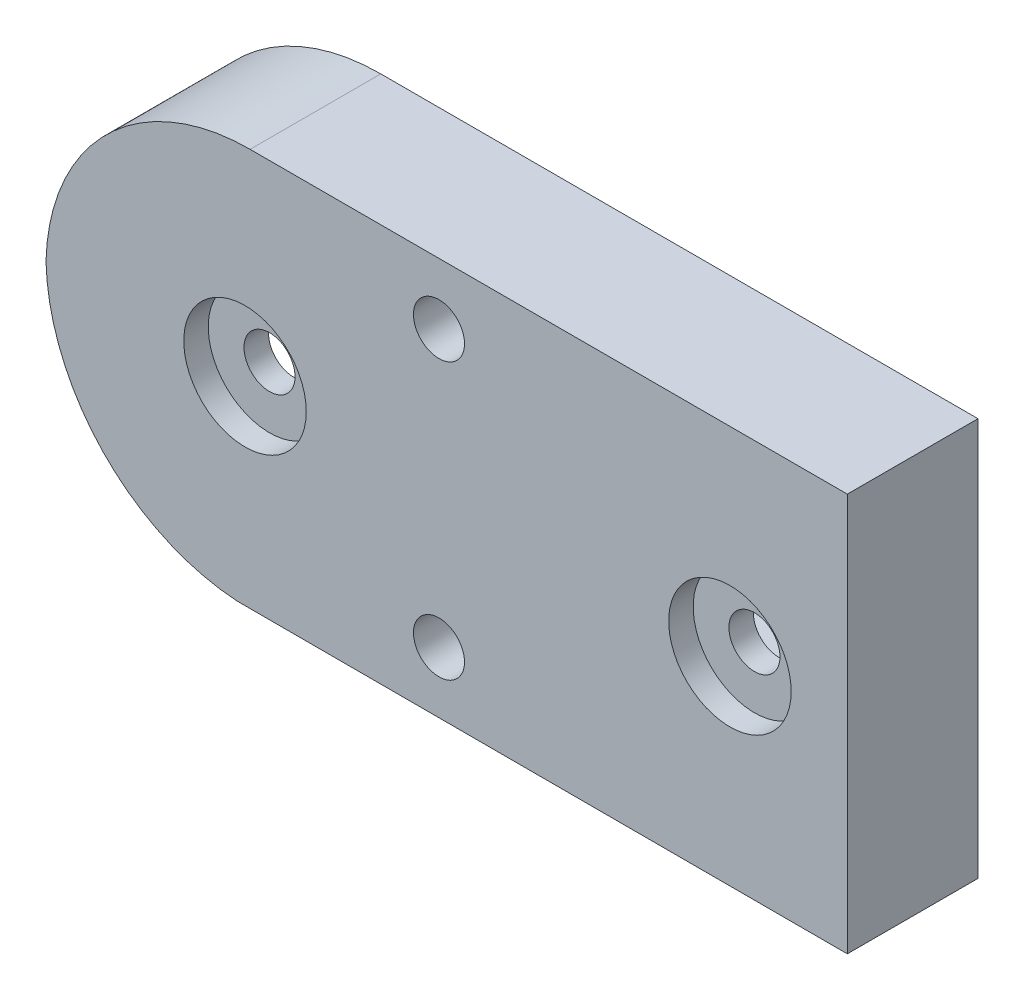
SolidWorks part; units mm, degrees
ref_plane "Front Plane" through (0, 0, 0) normal (0, 0, 1) x (1, 0, 0)
ref_plane "Top Plane" through (0, 0, 0) normal (0, 1, 0) x (1, 0, 0)
ref_plane "Right Plane" through (0, 0, 0) normal (1, 0, 0) x (0, 0, -1)
sketch "Sketch1" plane through (0, 0, 0) normal (0, 0, 1) x (1, 0, 0)
  line L0 (0, 0) -> (23.75, 0)
  line L1 (23.75, 3.75) -> (6.7823, 3.75)
  line L2 (23.75, -3.75) -> (6.7823, -3.75)
  line L3 (0, 0) -> (-9.75, 0)
  line L4 (-9.75, -9.75) -> (-9.75, 9.75)
  line L5 (-9.75, 9.75) -> (29.5, 9.75)
  line L6 (29.5, 9.75) -> (29.5, -9.75)
  line L7 (-9.75, -9.75) -> (29.5, -9.75)
  line L8 (29.5, 9.75) -> (29.5, 6.75)
  line L9 (29.5, 6.75) -> (9.5, 6.75)
  line L10 (29.5, -9.75) -> (29.5, -6.75)
  line L11 (29.5, -6.75) -> (9.5, -6.75)
  circle A0 centre (0, 0) radius 7.75
  circle A1 centre (23.75, 0) radius 3.75
  arc A2 (4.901, 6.0035) -> (11.225, 3.75) centre (11.225, 13.75) ccw
  arc A3 (11.225, -3.75) -> (4.901, -6.0035) centre (11.225, -13.75) ccw
  circle A4 centre (9.5, 6.75) radius 1.25
  circle A6 centre (9.5, -6.75) radius 1.25
  point P21 (29.5, 0)
  dimension "D1" = 15.5
  dimension "D3" = 7.5
  dimension "D4" = 9.75
  dimension "D8" = 10
  dimension "D9" = 10
  dimension "D7" = 2.5
  dimension "D11" = 20
  dimension "D10" = 2.5
  dimension "D2" = 23.75
  dimension "D5" = 9.75
  dimension "D6" = 39.25
  dimension "D12" = 20
extrude "Boss-Extrude4" add sketch "Sketch1" along normal blind 4 contours A6 L6 A4 L5 L4 A0 A2 L1 A1 L2 A3 L7 region at (-9.3117, 4.875, 0)
fillet "Fillet1" radius 10 2 edges at (-9.75, -9.75, 2) (-9.75, 9.75, 2)
sketch "Sketch2" plane through (0, 0, 4) normal (0, 0, 1) x (1, 0, 0)
  line L0 (0, 9.7532) -> (29.5, 9.75)
  line L1 (29.5, 9.75) -> (29.5, -9.75)
  line L2 (29.5, -9.75) -> (-0.681, -9.7294)
  circle A0 centre (0, 0) radius 1.25
  circle A1 centre (23.75, 0) radius 1.25
  circle A2 centre (0, 0) radius 9.7532
  circle M1 centre (9.5, -6.75) radius 1.25
  circle M2 centre (9.5, 6.75) radius 1.25
  arc M3 (0.25, 9.75) -> (-9.7469, 0) centre (0.25, -0.25) ccw
  arc M4 (-9.7469, 0) -> (0.25, -9.75) centre (0.25, 0.25) ccw
  line M6 (29.5, -9.75) -> (29.5, 9.75)
  line M7 (29.5, 9.75) -> (0.25, 9.75)
  arc M8 (11.225, -3.75) -> (4.901, -6.0035) centre (11.225, -13.75) ccw
  arc M9 (4.901, -6.0035) -> (4.901, 6.0035) centre (0, 0) cw
  arc M10 (4.901, 6.0035) -> (11.225, 3.75) centre (11.225, 13.75) ccw
  line M11 (11.225, 3.75) -> (23.75, 3.75)
  arc M12 (23.75, 3.75) -> (23.75, -3.75) centre (23.75, 0) cw
  line M13 (23.75, -3.75) -> (11.225, -3.75)
extrude "Boss-Extrude5" add sketch "Sketch2" along normal blind 1.2 contours A2 L2 M10 M3 M4 M8 M9 | A2 A0 M8 M10 M9 | A2 L2 M10 M11 M12 M13 M8 M6 M7 M2 M1 | A2 A1 M8 M13 M12 M11 M10 region at (29.1485, 0, 4) region at (5.2395, 7.9049, 4) region at (17.8705, 0, 4) region at (9.3045, 2.0112, 4)
sketch "Sketch3" plane through (0, 0, 5.2) normal (0, 0, 1) x (1, 0, 0)
  line L0 (0, 9.75) -> (29.5, 9.75)
  line L1 (29.5, 9.75) -> (29.5, -9.75)
  line L2 (29.5, -9.75) -> (0, -9.75)
  circle A0 centre (0, 0) radius 3
  circle A1 centre (23.75, 0) radius 3
  circle A2 centre (0, 0) radius 9.75
  line M2 (29.5, 9.75) -> (0.25, 9.75)
  arc M3 (0.25, 9.75) -> (-9.7469, 0) centre (0.25, -0.25) ccw
  arc M4 (-9.7469, 0) -> (-0.3884, -9.7296) centre (0.25, 0.25) ccw
  line M5 (-0.3884, -9.7296) -> (29.5, -9.75)
  line M6 (29.5, -9.75) -> (29.5, 9.75)
  circle M8 centre (9.5, 6.75) radius 1.25
  circle M9 centre (9.5, -6.75) radius 1.25
extrude "Boss-Extrude6" add sketch "Sketch3" along normal blind 1.2 contours A2 A0 M5 M3 M4 | A2 A1 M5 M6 M2 M3 M9 M8 region at (18.3187, 0.0073, 5.2) region at (6.7419, 6.6566, 5.2)
